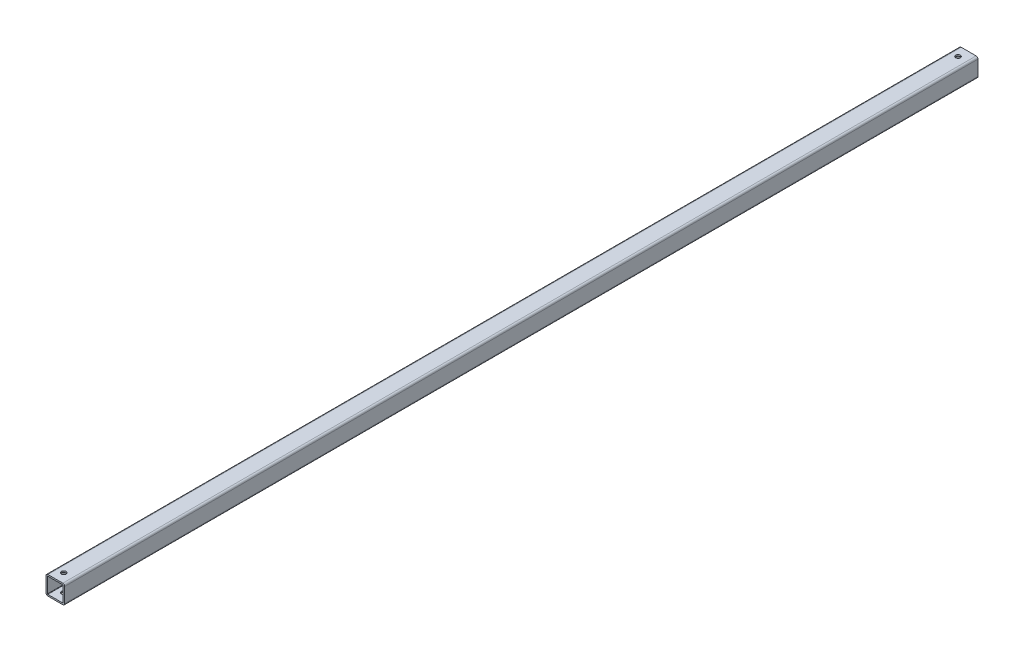
SolidWorks part; units mm, degrees
material "6063-T4"
ref_plane "Front Plane" through (0, 0, 0) normal (0, 0, 1) x (1, 0, 0)
ref_plane "Top Plane" through (0, 0, 0) normal (0, 1, 0) x (1, 0, 0)
ref_plane "Right Plane" through (0, 0, 0) normal (1, 0, 0) x (0, 0, -1)
sketch "Sketch1" plane through (0, 0, 0) normal (0, 0, 1) x (1, 0, 0)
  line L1 (10, -12.5) -> (-10, -12.5)
  line L2 (12.5, -10) -> (12.5, 10)
  line L3 (10, 12.5) -> (-10, 12.5)
  line L4 (-12.5, -10) -> (-12.5, 10)
  line L5 (12.5, -12.5) -> (-12.5, 12.5) construction
  line L6 (12.5, 12.5) -> (-12.5, -12.5) construction
  arc A0 (-10, 12.5) -> (-12.5, 10) centre (-10, 10) ccw
  arc A1 (12.5, 10) -> (10, 12.5) centre (10, 10) ccw
  arc A2 (10, -12.5) -> (12.5, -10) centre (10, -10) ccw
  arc A3 (-10, -12.5) -> (-12.5, -10) centre (-10, -10) cw
  point P0 (0, 0)
  dimension "D2" = 2.5
  dimension "D1" = 25
extrude "Extrude-Thin1" add sketch "Sketch1" along normal mid plane 1219.2 thin thin type one direction reverse wall 2
hole_wizard "1/4 (0.25) Diameter Hole1" positions "Sketch2" profile "Sketch3" hole size "1/4" standard "ANSI Inch"
sketch "Sketch2" plane through (0, 12.5, 0) normal (0, 1, 0) x (1, 0, 0)
  point P0 (-1.3992, 596.9)
  point P3 (-1.3992, -596.9)
sketch "Sketch3" plane through (-1.3992, 12.5, -596.9) normal (1, 0, 0) x (0, 0, 1)
  line L0 (0, 0) -> (0, 29.8477)
  line L1 (0, 29.8477) -> (3.175, 27.94)
  line L2 (3.175, 27.94) -> (3.175, 0)
  line L5 (3.175, 0) -> (0, 0)
  line L10 (0, 29.8477) -> (-3.175, 27.94) construction
  line L11 (0, -6.35) -> (0, 107.95) construction
  dimension "Hole Dia." = 6.35
  dimension "Hole Depth" = 27.94
  dimension "Drill Angle" = 118
equation "\"D2@Sketch1\" = \"D5@Extrude-Thin1\" * 1.25"
